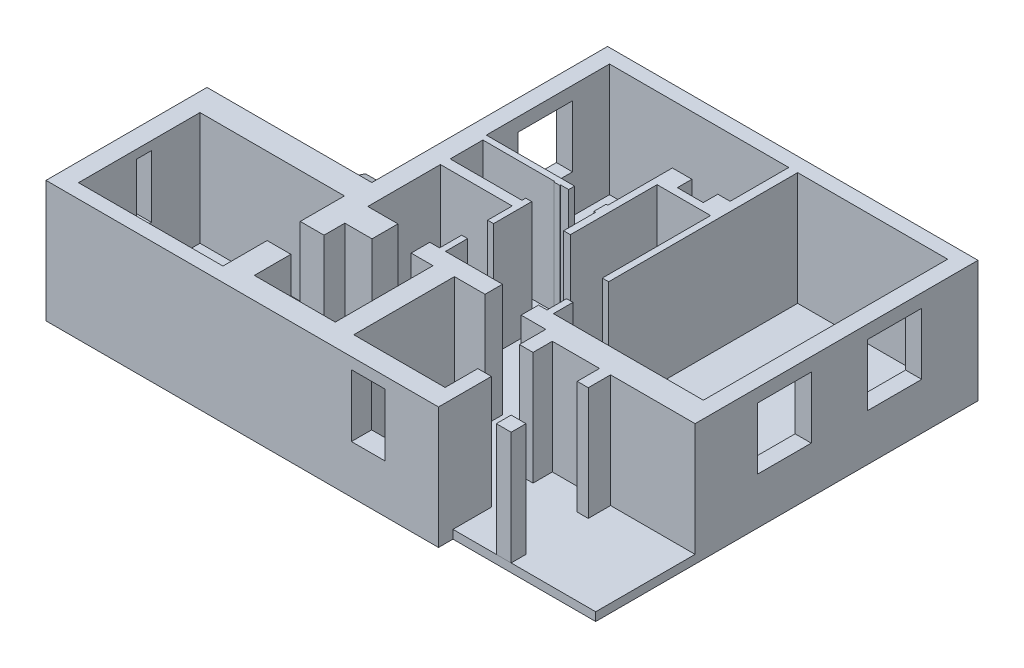
SolidWorks part; units mm, degrees
ref_plane "Спереди" through (0, 0, 0) normal (0, 0, 1) x (1, 0, 0)
ref_plane "Сверху" through (0, 0, 0) normal (0, 1, 0) x (1, 0, 0)
ref_plane "Справа" through (0, 0, 0) normal (1, 0, 0) x (0, 0, -1)
sketch "Эскиз1" plane through (0, 0, 0) normal (0, 1, 0) x (1, 0, 0)
  line L0 (0, 0) -> (4220, 0)
  line L1 (4220, 0) -> (4220, -1380)
  line L2 (4220, -1380) -> (3930, -1380)
  line L3 (3930, -1380) -> (3930, -1722.2944)
  line L4 (3320, -1722.2944) -> (3320, -1380)
  line L5 (3320, -1380) -> (2860, -1380)
  line L6 (2860, -1380) -> (2860, -2900)
  line L7 (2860, -2900) -> (2820, -2900)
  line L8 (0, -2900) -> (0, 0)
  line L9 (2820, -2900) -> (2820, -3185.6444)
  line L10 (2820, -3185.6444) -> (2860, -3185.6444)
  line L11 (2860, -3185.6444) -> (2860, -3940)
  line L12 (2080, -2900) -> (2080, -3040)
  line L13 (2080, -3040) -> (1890, -3040)
  line L14 (1890, -3040) -> (1890, -3060)
  line L15 (2080, -2900) -> (0, -2900)
  line L16 (3020, -3940) -> (3020, -1900.0287)
  line L17 (1890, -3060) -> (1750, -3060)
  line L18 (1750, -3060) -> (1750, -3040)
  line L19 (1750, -3040) -> (60, -3040)
  line L20 (60, -3040) -> (60, -3810)
  line L21 (60, -3810) -> (1750, -3810)
  line L22 (1750, -3810) -> (1750, -3720)
  line L23 (1750, -3720) -> (1890, -3720)
  line L24 (1890, -3720) -> (1890, -4620)
  line L25 (1890, -4620) -> (1750, -4620)
  line L26 (1750, -4620) -> (1750, -4040)
  line L27 (1750, -4040) -> (60, -4040)
  line L28 (60, -4040) -> (60, -5750)
  line L29 (60, -5750) -> (770, -5750)
  line L30 (770, -5750) -> (770, -6360)
  line L31 (770, -6360) -> (753.6696, -6360)
  line L32 (130, -6360) -> (130, -6850)
  line L33 (130, -6850) -> (-430, -6850)
  line L34 (-430, -6850) -> (-430, -5810)
  line L35 (-430, -5810) -> (-3830, -5810)
  line L36 (-3830, -5810) -> (-3830, -8670)
  line L37 (-3830, -8670) -> (-430, -8670)
  line L38 (-430, -8670) -> (-430, -7630)
  line L39 (-430, -7630) -> (130, -7630)
  line L40 (130, -7630) -> (130, -8490)
  line L41 (130, -8490) -> (2035, -8490)
  line L42 (2035, -8490) -> (2035, -6190)
  line L43 (2035, -6190) -> (1520, -6190)
  line L44 (1520, -6190) -> (1520, -5750)
  line L45 (1520, -5750) -> (1750, -5750)
  line L46 (1750, -5750) -> (1750, -5230)
  line L47 (1750, -5230) -> (1890, -5230)
  line L48 (1890, -5230) -> (1890, -5750)
  line L49 (1890, -5750) -> (3230, -5750)
  line L50 (3230, -5750) -> (3230, -6160)
  line L51 (3230, -6160) -> (2510, -6160)
  line L52 (2510, -6160) -> (2510, -8530)
  line L53 (2510, -8530) -> (4660, -8530)
  line L54 (4660, -8530) -> (4660, -7760)
  line L55 (4660, -7760) -> (4980, -7760)
  line L56 (2860, -3940) -> (3020, -3940)
  line L57 (4280, -1900.0287) -> (4280, -4450)
  line L58 (4280, -4450) -> (4430, -4450)
  line L59 (4430, -4450) -> (4430, 0)
  line L60 (4430, 0) -> (7960, 0)
  line L61 (7960, 0) -> (7960, -5750)
  line L62 (7960, -5750) -> (4430, -5750)
  line L63 (4430, -5750) -> (4430, -5290)
  line L64 (4430, -5290) -> (4280, -5290)
  line L65 (-4260, -5215) -> (-4260, -9005)
  line L66 (-2190, -5800.9457) -> (-2190, -8670) construction
  line L67 (4080, -6160) -> (4080, -5750)
  line L68 (4080, -5750) -> (4280, -5750)
  line L69 (4280, -5750) -> (4280, -5290)
  line L70 (4080, -6160) -> (4660, -6160)
  line L71 (4660, -6160) -> (4660, -6780)
  line L72 (4660, -6780) -> (4980, -6780)
  line L73 (753.6696, -6360) -> (130, -6360)
  line L74 (-217.7441, -870) -> (-217.7441, -2150) construction
  line L75 (8168.2501, -990) -> (8168.2501, -2270) construction
  line L76 (8168.2501, -3590) -> (8168.2501, -4860) construction
  line L77 (8249.589, -2900) -> (8168.2501, -2900) construction
  line L78 (8168.2501, -2900) -> (9306.9939, -2900) construction
  line L79 (8340, 335) -> (8340, -6325)
  line L80 (-380, 335) -> (-380, -3705)
  line L81 (2930, -8710.1469) -> (3720, -8710.1469) construction
  line L82 (-380, -3705) -> (-2040, -3705)
  line L83 (-4260, -9005) -> (4980, -9005)
  line L84 (-380, 335) -> (8340, 335)
  line L85 (0, 0) -> (-380, 0) construction
  line L86 (7960, 0) -> (8340, 0) construction
  line L87 (-2040, -3705) -> (-2040, -5215)
  line L88 (-2040, -5215) -> (-4260, -5215)
  line L90 (-430, -8670) -> (-430, -9005) construction
  line L91 (7960, 0) -> (7960, 335) construction
  line L92 (3320, -1722.2944) -> (3930, -1722.2944)
  line L93 (3020, -1900.0287) -> (4280, -1900.0287)
  line L94 (4980, -9005) -> (4980, -7760)
  line L95 (4980, -6325) -> (4980, -6780)
  line L96 (6000, -8315) -> (6000, -8665)
  line L97 (8340, -6325) -> (6350, -6325)
  line L98 (6000, -8665) -> (6350, -8665)
  line L99 (6350, -8665) -> (6350, -8315)
  line L100 (6350, -8315) -> (6000, -8315)
  line L101 (6090, -6325) -> (6090, -6850)
  line L102 (6090, -6850) -> (6350, -6850)
  line L103 (6350, -6850) -> (6350, -6325)
  line L105 (6090, -6325) -> (4980, -6325)
  point P92 (761.8348, -6360)
  dimension "D1" = 4220
  dimension "D2" = 2900
  dimension "D3" = 1380
  dimension "D4" = 1360
  dimension "D5" = 290
  dimension "D6" = 900
  dimension "D7" = 40
  dimension "D8" = 780
  dimension "D9" = 970
  dimension "D10" = 1130
  dimension "D11" = 140
  dimension "D12" = 770
  dimension "D13" = 1690
  dimension "D14" = 1830
  dimension "D15" = 20
  dimension "D16" = 680
  dimension "D17" = 410
  dimension "D18" = 2190
  dimension "D19" = 580
  dimension "D21" = 1710
  dimension "D22" = 710
  dimension "D23" = 1460
  dimension "D24" = 2390
  dimension "D25" = 2190
  dimension "D26" = 1340
  dimension "D27" = 460
  dimension "D28" = 1300
  dimension "D29" = 3940
  dimension "D30" = 5750
  dimension "D31" = 620
  dimension "D32" = 1600
  dimension "D33" = 380
  dimension "D34" = 350
  dimension "D35" = 2150
  dimension "D36" = 2370
  dimension "D37" = 150
  dimension "D38" = 1990
  dimension "D39" = 1040
  dimension "D40" = 8720
  dimension "D41" = 6070
  dimension "D42" = 870
  dimension "D43" = 2150
  dimension "D44" = 890
  dimension "D45" = 2160
  dimension "D46" = 3480
  dimension "D47" = 4760
  dimension "D48" = 2850
  dimension "D49" = 9340
  dimension "D50" = 1660
  dimension "D51" = 2130
  dimension "D52" = 2740
  dimension "D53" = 490
  dimension "D54" = 1270
  dimension "D55" = 3960
  dimension "D56" = 640
  dimension "D57" = 1265
  dimension "D58" = 440
  dimension "D59" = 3400
  dimension "D60" = 1040
  dimension "D61" = 1760
  dimension "D62" = 940
  dimension "D63" = 1730
  dimension "D64" = 1510
  dimension "D65" = 335
  dimension "D66" = 4040
  dimension "D67" = 3360
  dimension "D68" = 2680
  dimension "D69" = 260
  dimension "D70" = 525
  dimension "D71" = 340
  dimension "D72" = 9240
extrude "Бобышка-Вытянуть1" add sketch "Эскиз1" along normal blind 2665
sketch "Эскиз2" plane through (0, 0, 0) normal (0, -1, 0) x (1, 0, 0)
  line L0 (-4260, 5215) -> (-4260, 9005) construction
  line L1 (-2040, 5215) -> (-4260, 5215) construction
  line L2 (-2040, 3705) -> (-2040, 5215) construction
  line L3 (-380, 3705) -> (-2040, 3705) construction
  line L4 (-380, -335) -> (-380, 3705) construction
  line L5 (8340, -335) -> (-380, -335) construction
  line L7 (-4260, 9005) -> (4980, 9005) construction
  line L8 (-4260, 5215) -> (-4260, 9005)
  line L9 (-2040, 5215) -> (-4260, 5215)
  line L10 (-2040, 3705) -> (-2040, 5215)
  line L11 (-380, 3705) -> (-2040, 3705)
  line L12 (-380, -335) -> (-380, 3705)
  line L13 (8340, -335) -> (-380, -335)
  line L15 (-4260, 9005) -> (4980, 9005)
  line L16 (8340, 6325) -> (8340, -335) construction
  line L17 (8340, 8665) -> (8340, -335)
  line L18 (6000, 8665) -> (6350, 8665) construction
  line L19 (4980, 8665) -> (8340, 8665)
  line L20 (4980, 9005) -> (4980, 7760) construction
  line L21 (4980, 9005) -> (4980, 8665)
extrude "Бобышка-Вытянуть2" add sketch "Эскиз2" along normal blind 200
sketch "Эскиз3" plane through (8340, 0, 0) normal (1, 0, 0) x (0, 0, -1)
  line L0 (-5750, 2665) -> (-5750, 0) construction
  line L1 (-4860, 900) -> (-3590, 900)
  line L2 (-4860, 900) -> (-4860, 2350)
  line L3 (-4860, 2350) -> (-3590, 2350)
  line L4 (-3590, 900) -> (-3590, 2350)
  line L5 (-2270, 900) -> (-990, 900)
  line L6 (-2270, 900) -> (-2270, 2350)
  line L7 (-2270, 2350) -> (-990, 2350)
  line L8 (-990, 900) -> (-990, 2350)
  line L9 (0, 0) -> (-4450, 0) construction
  dimension "D1" = 890
  dimension "D2" = 2160
  dimension "D3" = 3480
  dimension "D4" = 4760
  dimension "D5" = 900
  dimension "D6" = 1450
extrude "Вырез-Вытянуть1" cut sketch "Эскиз3" against normal up to surface (380 mm away) up to face at (7960, 1332.5, 2875)
sketch "Эскиз4" plane through (-380, 0, 0) normal (-1, 0, 0) x (0, 0, 1)
  line L0 (1380, 0) -> (0, 0) construction
  line L1 (870, 2350) -> (2150, 2350)
  line L2 (870, 2350) -> (870, 900)
  line L3 (870, 900) -> (2150, 900)
  line L4 (2150, 2350) -> (2150, 900)
  line L5 (0, 2665) -> (0, 0) construction
  dimension "D1" = 900
  dimension "D2" = 1450
  dimension "D3" = 870
  dimension "D4" = 2150
extrude "Вырез-Вытянуть2" cut sketch "Эскиз4" against normal up to next (380 mm away)
sketch "Эскиз5" plane through (-4260, 0, 0) normal (-1, 0, 0) x (0, 0, 1)
  line L0 (8670, 0) -> (7630, 0) construction
  line L1 (6954.3167, 1000) -> (7300.9323, 1000)
  line L2 (6954.3167, 1000) -> (6954.3167, 2460)
  line L3 (6954.3167, 2460) -> (7300.9323, 2460)
  line L4 (7300.9323, 1000) -> (7300.9323, 2460)
  dimension "D1" = 1000
  dimension "D2" = 1460
extrude "Вырез-Вытянуть3" cut sketch "Эскиз5" against normal up to next (430 mm away)
sketch "Эскиз6" plane through (0, 0, 9005) normal (0, 0, 1) x (1, 0, 0)
  line L0 (4660, 2665) -> (4660, 0) construction
  line L1 (2930, 935) -> (3720, 935)
  line L2 (2930, 935) -> (2930, 2400)
  line L3 (2930, 2400) -> (3720, 2400)
  line L4 (3720, 935) -> (3720, 2400)
  line L5 (4660, 0) -> (4080, 0) construction
  dimension "D1" = 940
  dimension "D2" = 1730
  dimension "D3" = 935
  dimension "D4" = 1465
extrude "Вырез-Вытянуть4" cut sketch "Эскиз6" against normal up to next (475 mm away)
sketch "Эскиз8" plane through (-2040, 0, 0) normal (-1, 0, 0) x (0, 0, 1)
  line L0 (5215, 2665) -> (5215, -200) construction
  line L1 (5215, 1750) -> (3705, 1260)
  line L2 (5215, 1750) -> (5215, 2665)
  line L3 (5215, 2665) -> (3705, 2665)
  line L4 (3705, 1260) -> (3705, 2665)
  line L5 (3705, 2665) -> (3705, -200) construction
  dimension "D1" = 1460
  dimension "D2" = 1950
extrude "Вырез-Вытянуть5" cut sketch "Эскиз8" against normal up to surface (1660 mm away) up to face at (-380, 1625, 1510)
sketch "Эскиз9" plane through (-2040, 0, 0) normal (-1, 0, 0) x (0, 0, 1)
  line L0 (5215, -200) -> (3705, -200) construction
  line L1 (4225, -200) -> (5145, -200)
  line L2 (4225, -200) -> (4225, 1050)
  line L3 (4225, 1050) -> (5145, 1050)
  line L4 (5145, -200) -> (5145, 1050)
  line L5 (5215, 1750) -> (5215, -200) construction
  dimension "D1" = 70
  dimension "D2" = 990
  dimension "D3" = 1250
extrude "Вырез-Вытянуть6" cut sketch "Эскиз9" against normal blind 300
